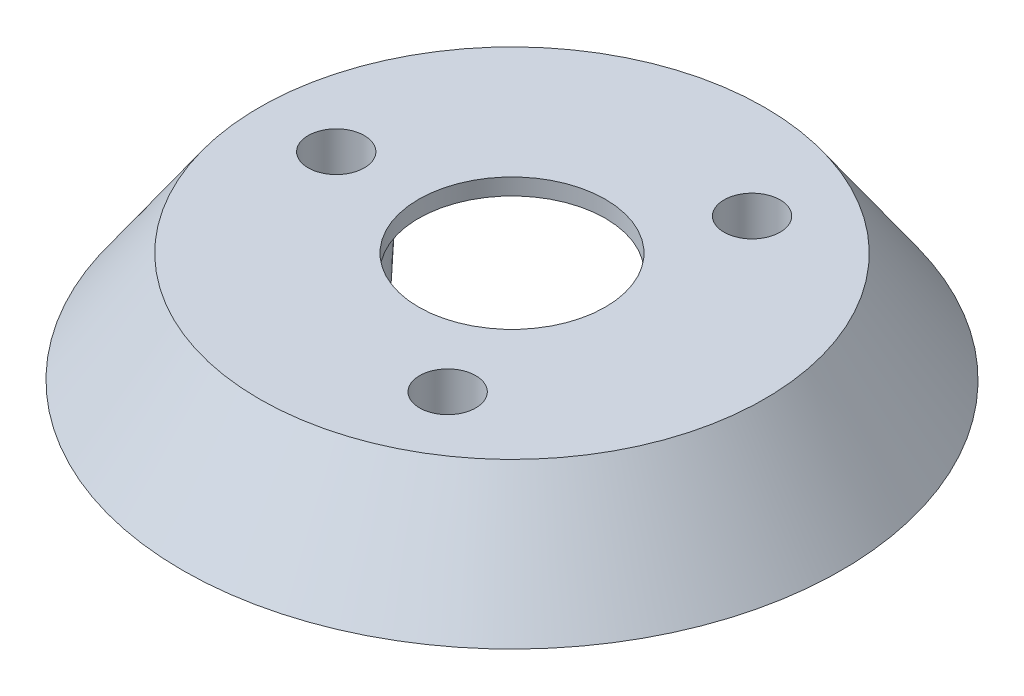
SolidWorks part; units mm, degrees
ref_plane "Plan de face" through (0, 0, 0) normal (0, 0, 1) x (1, 0, 0)
ref_plane "Plan de dessus" through (0, 0, 0) normal (0, 1, 0) x (1, 0, 0)
ref_plane "Plan de droite" through (0, 0, 0) normal (1, 0, 0) x (0, 0, -1)
sketch "Esquisse1" plane through (0, 0, 0) normal (0, 1, 0) x (1, 0, 0)
  circle A0 centre (0, 0) radius 30
  dimension "D1" = 60
extrude "Boss.-Extru.1" add sketch "Esquisse1" along normal blind 10 contours A0
chamfer "Chanfrein1" distance 10 angle 35 1 edges at (0, 10, 30) first distance on face at (0, 10, 30)
shell "Coque2" thickness 1.5 removed face at (0, 0, 30)
sketch "Esquisse2" plane through (0, 8.5, 0) normal (0, -1, 0) x (1, 0, 0)
  circle A0 centre (-16, 0) radius 4
  dimension "D2" = 8
  dimension "D1" = 16
extrude "Boss.-Extru.2" add sketch "Esquisse2" along normal blind 8.5
chamfer "Chanfrein2" distance 8.5 angle 3 1 edges at (-16, 0, -4) first distance on face at (-16, 0, -4)
sketch "Esquisse5" plane through (0, 0, 0) normal (0, -1, 0) x (1, 0, 0)
  circle A0 centre (-16, 0) radius 2.5545
  circle A1 centre (-16, 0) radius 3.5545 construction
  dimension "D1" = 1
  dimension "D2" = 5.1091
extrude "Enlèv. mat.-Extru.1" cut sketch "Esquisse5" against normal up to surface (10 mm away) up to face at (0, 10, 22.9979)
pattern_circular "Répétition circulaire1" count 3 over 360 about axis through (0, 8.5, 0) along (0, 1, 0) of "Boss.-Extru.2", "Chanfrein2", "Enlèv. mat.-Extru.1"
sketch "Esquisse6" plane through (0, 8.5, 0) normal (0, -1, 0) x (1, 0, 0)
  circle A0 centre (0, 0) radius 8.5
  dimension "D1" = 17
extrude "Enlèv. mat.-Extru.2" cut sketch "Esquisse6" against normal blind 8.5
